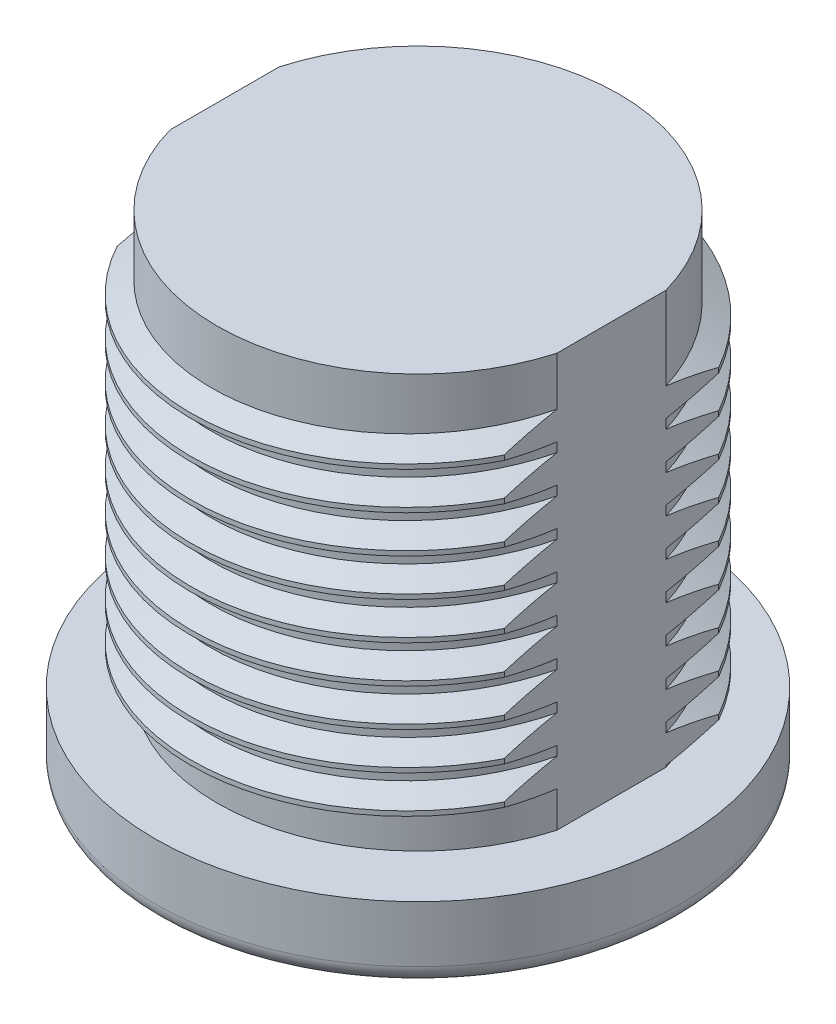
SolidWorks part; units mm, degrees
ref_plane "Alzado" through (0, 0, 0) normal (0, 0, 1) x (1, 0, 0)
ref_plane "Planta" through (0, 0, 0) normal (0, 1, 0) x (1, 0, 0)
ref_plane "Vista lateral" through (0, 0, 0) normal (1, 0, 0) x (0, 0, -1)
sketch "Croquis1" plane through (0, 0, 0) normal (0, 1, 0) x (1, 0, 0)
  circle A0 centre (0, 0) radius 7
  dimension "D1" = 14
extrude "Saliente-Extruir1" add sketch "Croquis1" along normal blind 2
sketch "Croquis2" plane through (0, 2, 0) normal (0, 1, 0) x (1, 0, 0)
  circle A0 centre (0, 0) radius 5.35
  dimension "D1" = 10.7
extrude "Saliente-Extruir2" add sketch "Croquis2" along normal blind 11
thread "Rosca1" pitch 1 method extrude profile "Perfil de rosca1" start angle 0, offset 0, length 9, pitch 1, diameter 10.7
ref_plane "Plano1" through (5.35, 2, 0) normal (0, 0, 1) x (1, 0, 0)
sketch "Perfil de rosca1" plane through (5.35, 2, 0) normal (0, 0, 1) x (1, 0, 0)
  line L0 (0, 0) -> (0, 1) construction
  line L1 (0, 0) -> (0.5413, 0.3125)
  line L2 (0.5413, 0.3125) -> (0.5413, 0.4375)
  line L3 (0.5413, 0.4375) -> (0, 0.75)
  line L4 (0.5413, 0.375) -> (0, 0.375) construction
  line L11 (0, 0) -> (0, 0.75)
  point P2 (0, 0)
  dimension "Pitch" = 1
  dimension "Profile_Angle" = 60
  dimension "Profile_Land" = 0.125
  dimension "Profile_Height" = 0.5413
sketch "Croquis6" plane through (0, 13, 0) normal (0, 1, 0) x (1, 0, 0)
  line L0 (0, 0) -> (0, 5.35) construction
  line L1 (6.15, -2.85) -> (5.15, -2.85)
  line L2 (6.15, -2.85) -> (6.15, 2.85)
  line L3 (6.15, 2.85) -> (5.15, 2.85)
  line L4 (5.15, -2.85) -> (5.15, 2.85)
  line L5 (-5.15, -2.85) -> (-5.15, 2.85)
  line L6 (-6.15, 2.85) -> (-5.15, 2.85)
  line L7 (-6.15, -2.85) -> (-6.15, 2.85)
  line L8 (-6.15, -2.85) -> (-5.15, -2.85)
  circle A0 centre (0, 0) radius 5.35 construction
  point P4 (5.15, 0)
  dimension "D1" = 0.2
  dimension "D2" = 1
  dimension "D3" = 5.7
extrude "Cortar-Extruir1" cut sketch "Croquis6" against normal blind 11
fillet "Redondeo1" radius 0.5 1 edges at (0, 0, 7)
sketch "Croquis7" plane through (0, 0, 0) normal (0, -1, 0) x (1, 0, 0)
  line L0 (0, -1.25) -> (0, -4.5) construction
  line L1 (0, -4.5) -> (0, -6.5) construction
  circle A0 centre (0, -1.25) radius 3.25
  circle A1 centre (0, 0) radius 6.5 construction
  point P2 (0, 0)
  point P9 (0, 0)
  dimension "D1" = 6.5
  dimension "D2" = 2
extrude "Cortar-Extruir2" cut sketch "Croquis7" against normal blind 8
sketch "Croquis8" plane through (0, 8, 0) normal (0, -1, 0) x (1, 0, 0)
  circle A0 centre (0, -1.25) radius 0.5
  dimension "D1" = 1
extrude "Saliente-Extruir3" add sketch "Croquis8" along normal blind 6
fillet "Redondeo2" radius 0.5 1 edges at (0, 2, -1.75)
